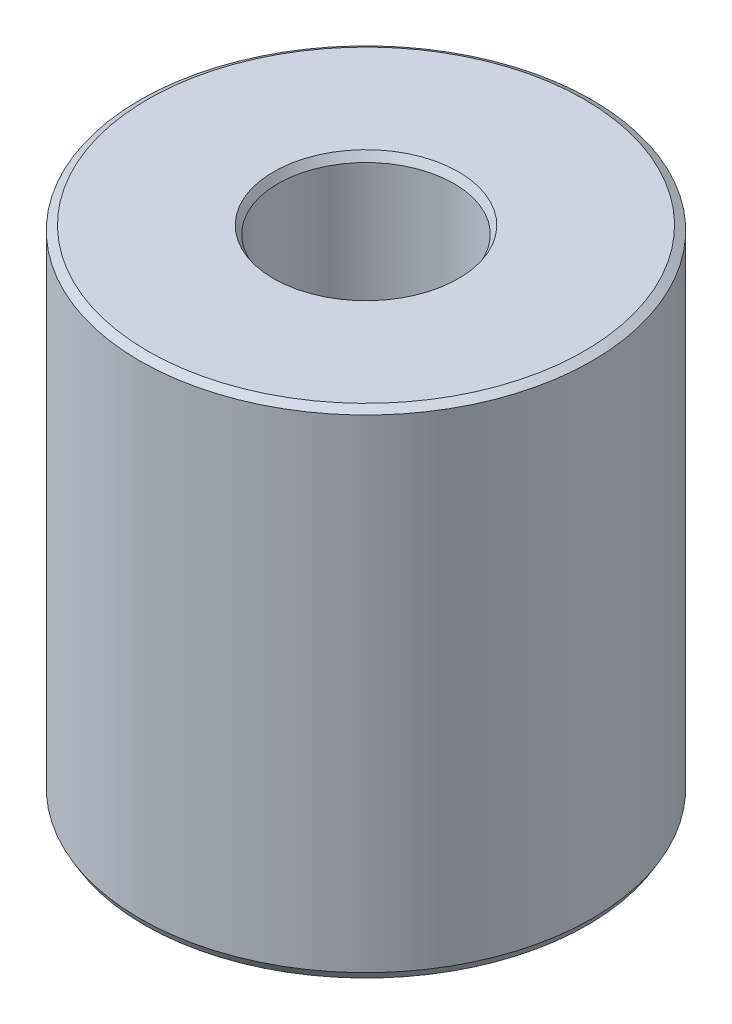
SolidWorks part; units mm, degrees
ref_plane "Front Plane" through (0, 0, 0) normal (0, 0, 1) x (1, 0, 0)
ref_plane "Top Plane" through (0, 0, 0) normal (0, 1, 0) x (1, 0, 0)
ref_plane "Right Plane" through (0, 0, 0) normal (1, 0, 0) x (0, 0, -1)
sketch "Sketch1" plane through (0, 0, 0) normal (0, 1, 0) x (1, 0, 0)
  circle A0 centre (0, 0) radius 40
  dimension "SLEEVE_OD" = 80
extrude "Boss-Extrude1" add sketch "Sketch1" along normal blind 87.6464
sketch "Sketch2" plane through (0, 0, 0) normal (0, 1, 0) x (1, 0, 0)
  circle A0 centre (0, 0) radius 15.5636
  dimension "BORE_D" = 31.1272
extrude "Cut-Extrude1" cut sketch "Sketch2" along normal through all
chamfer "Chamfer1" distance 0.806 angle 60 4 edges at (0, 87.6464, 15.5636) (0, 0, 15.5636) (0, 0, 40) (0, 87.6464, 40) first distance on face at (0, 87.6464, 15.5636) first distance on face at (0, 0, 15.5636) first distance on face at (0, 87.6464, 40)
